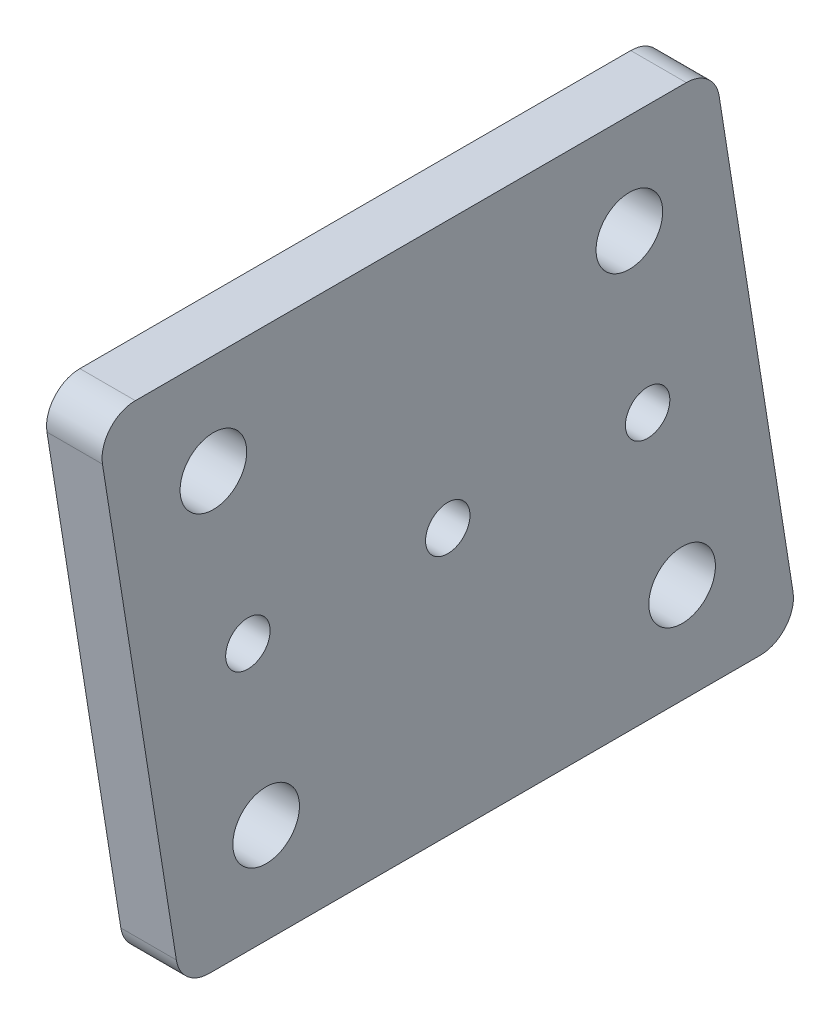
SolidWorks part; units mm, degrees
ref_plane "Front Plane" through (0, 0, 0) normal (0, 0, 1) x (1, 0, 0)
ref_plane "Top Plane" through (0, 0, 0) normal (0, 1, 0) x (1, 0, 0)
ref_plane "Right Plane" through (0, 0, 0) normal (1, 0, 0) x (0, 0, -1)
sketch "Sketch1" plane through (0, 0, 0) normal (1, 0, 0) x (0, 0, -1)
  line L0 (-1.1006, 45.3033) -> (9.4713, -21.4449) construction
  line L1 (-1.1006, 45.3033) -> (24.2111, 45.3033) construction
  line L2 (24.2111, 45.3033) -> (34.783, -21.4449) construction
  line L3 (34.783, -21.4449) -> (9.4713, -21.4449) construction
  line L4 (0, 0) -> (37.4612, 0) construction
  line L5 (0, 0) -> (-4.7515, 30) construction
  line L6 (37.4612, 0) -> (32.7097, 30) construction
  line L7 (-4.7515, 30) -> (32.7097, 30) construction
  line L8 (-2.3758, 15) -> (35.0854, 15) construction
  line L9 (-3.1677, 20) -> (34.2935, 20) construction
  line L10 (-1.5838, 10) -> (35.8774, 10) construction
  line L11 (-7.6867, -9) -> (47.9989, -9)
  line L12 (47.9989, -9) -> (40.3964, 39)
  line L13 (40.3964, 39) -> (-15.2892, 39)
  line L14 (-15.2892, 39) -> (-7.6867, -9)
  circle A0 centre (0, 0) radius 6 construction
  circle A1 centre (0, 0) radius 9 construction
  circle A2 centre (0, 0) radius 3
  circle A3 centre (37.4612, 0) radius 3
  circle A4 centre (37.4612, 0) radius 6 construction
  circle A5 centre (37.4612, 0) radius 9 construction
  circle A6 centre (-4.7515, 30) radius 3
  circle A7 centre (-4.7515, 30) radius 6 construction
  circle A8 centre (-4.7515, 30) radius 9 construction
  circle A9 centre (32.7097, 30) radius 3
  circle A10 centre (32.7097, 30) radius 6 construction
  circle A11 centre (32.7097, 30) radius 9 construction
  circle A12 centre (16.3548, 15) radius 2
  circle A13 centre (-1.6452, 15) radius 2
  circle A14 centre (34.3548, 15) radius 2
  dimension "D1" = 18
  dimension "D2" = 12
  dimension "D3" = 6
  dimension "D9" = 18
  dimension "D10" = 18
  dimension "D11" = 4
  dimension "D4" = 99
  dimension "D5" = 25
  dimension "D6" = 30
  dimension "D7" = 5
  dimension "D8" = 5
  dimension "D12" = 48
extrude "Boss-Extrude1" add sketch "Sketch1" along normal blind 5
fillet "Fillet1" radius 3 4 edges at (2.5, 39, -40.3964) (2.5, -9, -47.9989) (2.5, -9, 7.6867) (2.5, 39, 15.2892)
